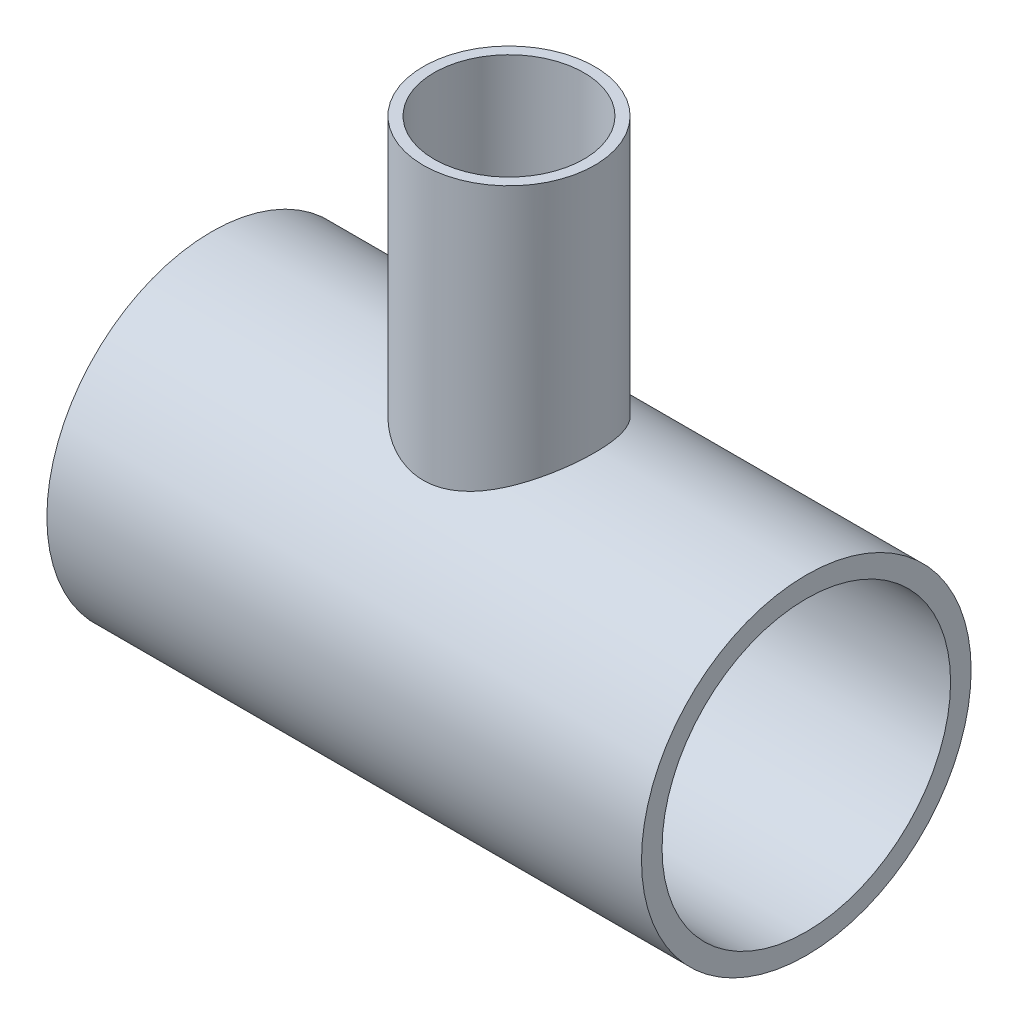
SolidWorks part; units mm, degrees
material "PE High Density"
ref_plane "Front Plane" through (0, 0, 0) normal (0, 0, 1) x (1, 0, 0)
ref_plane "Top Plane" through (0, 0, 0) normal (0, 1, 0) x (1, 0, 0)
ref_plane "Right Plane" through (0, 0, 0) normal (1, 0, 0) x (0, 0, -1)
sketch "Revolve of 12 NOM" plane through (0, 0, 0) normal (0, 0, 1) x (1, 0, 0)
  line L0 (0, 0) -> (319.0916, 0) construction
  line L1 (0, 161.925) -> (584.2, 161.925)
  line L2 (0, 161.925) -> (0, 141.732)
  line L3 (0, 141.732) -> (584.2, 141.732)
  line L4 (584.2, 161.925) -> (584.2, 141.732)
  dimension "D1" = 141.732
  dimension "D2" = 161.925
  dimension "D3" = 584.2
revolve "Revolve12 NOM" add sketch "Revolve of 12 NOM" angle 360 about L0
ref_plane "Offset B Plane" through (0, 406.4, 0) normal (0, 1, 0) x (1, 0, 0)
sketch "Sketch2" plane through (0, 406.4, 0) normal (0, 1, 0) x (1, 0, 0)
  line L0 (-178.1175, 0) -> (178.1175, 0) construction
  line L1 (584.2, -161.925) -> (584.2, 161.925) construction
  circle A0 centre (292.1, 0) radius 84.1375
  dimension "D2" = 168.275
  dimension "D1" = 292.1
extrude "6 NOM OD Extrude" add sketch "Sketch2" against normal up to surface (268.0505 mm away) up to face at (0, 0, 161.925)
sketch "6 NOM ID Extrude" plane through (0, 406.4, 0) normal (0, 1, 0) x (1, 0, 0)
  circle A0 centre (292.1, 0) radius 73.6473
  dimension "D1" = 147.2946
extrude "6 NOM ID Extrude Cut" cut sketch "6 NOM ID Extrude" against normal up to surface (406.4 mm away) up to plane "Top Plane"
ref_axis "Axis1" through (292.1, 115.9252, 0) along (0, 1, 0)
ref_plane "Midplane" through (292.1, 0, 0) normal (1, 0, 0) x (0, 0, -1)
sketch "Sketch3" plane through (0, 406.4, 0) normal (0, 1, 0) x (1, 0, 0)
  point P0 (292.1, 0)
equation "\"A\"= 8in'EPG Datasheet"
equation "\"B\"= 16in'EPG Datasheet"
equation "\"L\"= 23in'EPG Datasheet"
equation "\"ID 12\"= 11.16in'EPG Datasheet"
equation "\"OD 12\"= 12.75in'EPG Datasheet"
equation "\"ID 6\"= 5.799in'EPG Datasheet"
equation "\"OD 6\"= 6.625in'EPG Datasheet"
equation "\"D1@Revolve of 12 NOM\" = \"ID 12\" / 2"
equation "\"D2@Revolve of 12 NOM\" = \"OD 12\" / 2"
equation "\"D3@Revolve of 12 NOM\" = \"L\""
equation "\"D1@Sketch2\"=\"L\"/2"
equation "\"D2@Sketch2\"=\"OD 6\""
equation "\"D1@6 NOM ID Extrude\" = \"ID 6\""
